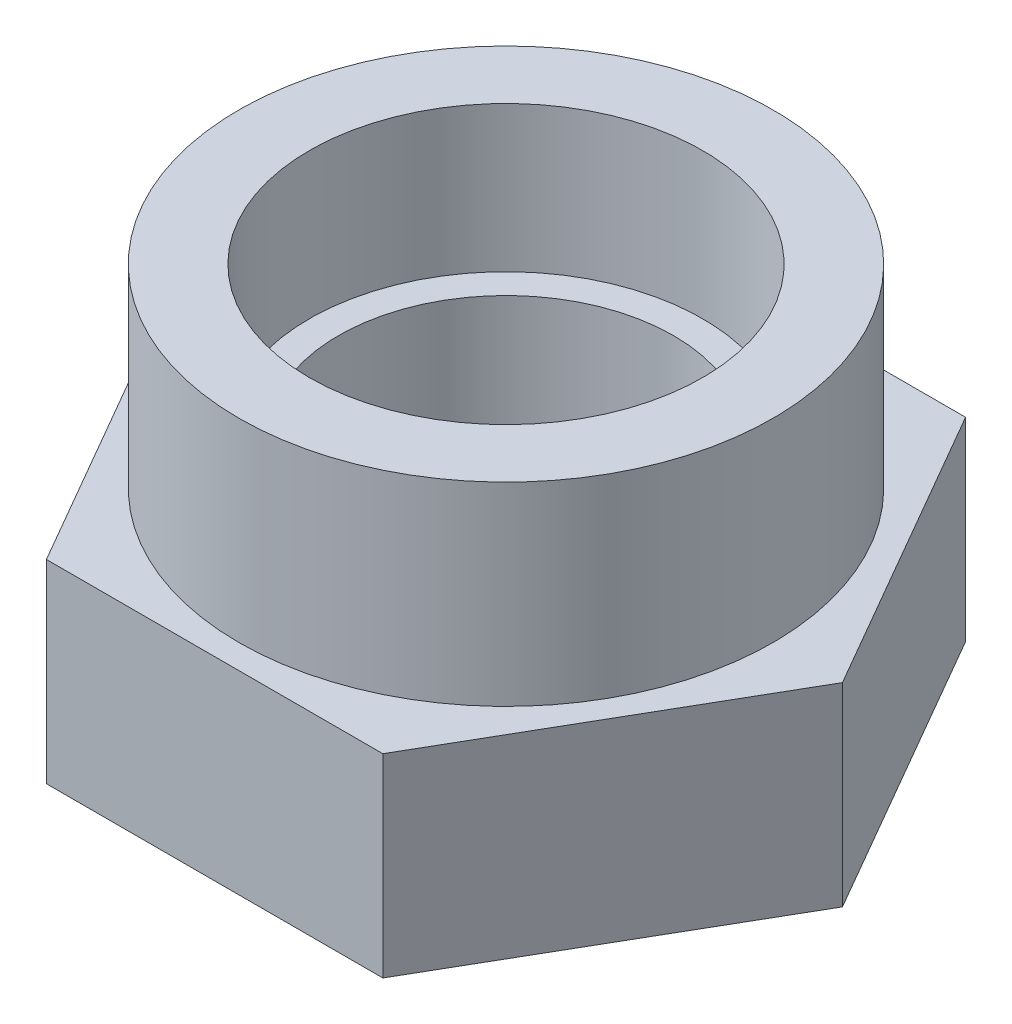
SolidWorks part; units mm, degrees
ref_plane "Front Plane" through (0, 0, 0) normal (0, 0, 1) x (1, 0, 0)
ref_plane "Top Plane" through (0, 0, 0) normal (0, 1, 0) x (1, 0, 0)
ref_plane "Right Plane" through (0, 0, 0) normal (1, 0, 0) x (0, 0, -1)
sketch "Sketch1" plane through (0, 0, 0) normal (0, 1, 0) x (1, 0, 0)
  line L1 (3.4641, 6) -> (-3.4641, 6)
  line L2 (-3.4641, 6) -> (-6.9282, 0)
  line L3 (-6.9282, 0) -> (-3.4641, -6)
  line L4 (-3.4641, -6) -> (3.4641, -6)
  line L5 (3.4641, -6) -> (6.9282, 0)
  line L6 (6.9282, 0) -> (3.4641, 6)
  circle A0 centre (0, 0) radius 6 construction
  circle A1 centre (0, 0) radius 3.45
  dimension "D2" = 6.9
  dimension "D1" = 12
extrude "Boss-Extrude1" add sketch "Sketch1" along normal blind 8
sketch "Sketch2" plane through (0, 8, 0) normal (0, 1, 0) x (1, 0, 0)
  circle A0 centre (0, 0) radius 4.05
  dimension "D1" = 8.1
extrude "Cut-Extrude1" cut sketch "Sketch2" against normal blind 3
sketch "Sketch3" plane through (0, 8, 0) normal (0, 1, 0) x (1, 0, 0)
  circle A0 centre (0, 0) radius 5.5
  circle A1 centre (0, 0) radius 10
  line M4 (6.9282, 0) -> (3.4641, 6)
  line M5 (3.4641, 6) -> (-3.4641, 6)
  line M6 (-3.4641, 6) -> (-6.9282, 0)
  line M7 (-6.9282, 0) -> (-3.4641, -6)
  line M8 (-3.4641, -6) -> (3.4641, -6)
  line M9 (3.4641, -6) -> (6.9282, 0)
  dimension "D1" = 20
  dimension "D2" = 11
extrude "Cut-Extrude3" cut sketch "Sketch3" against normal blind 4 contours A1 M4 M9 M8 M7 M6 M5 | A0 M9 M4 M5 M6 M7 M8 region at (-9.7172, 8, 0) region at (5.0374, 8, 2.9083)
